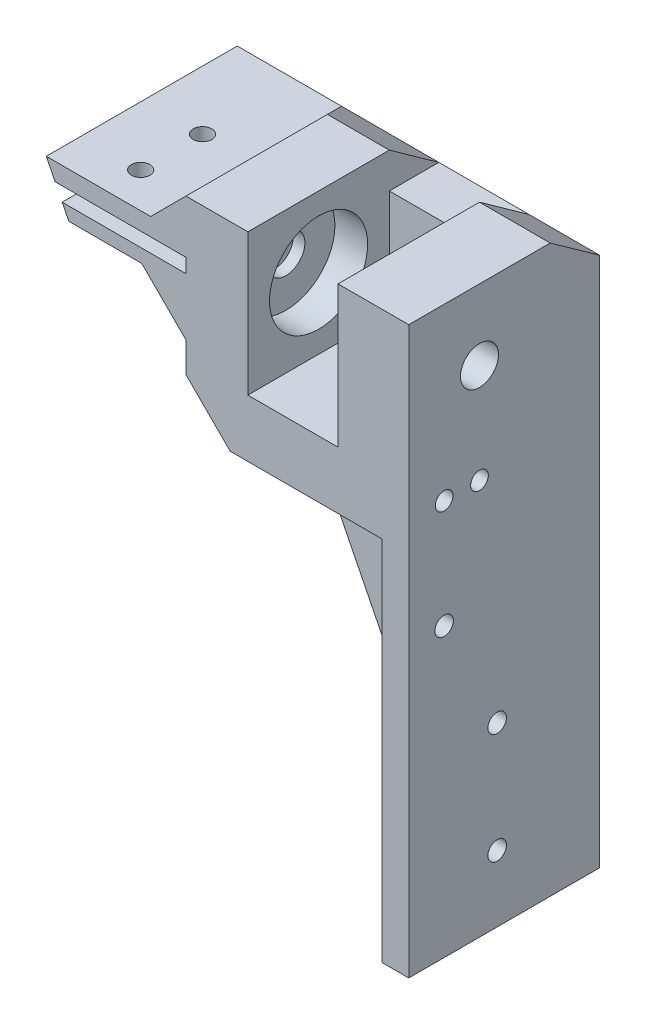
SolidWorks part; units mm, degrees
material "ABS"
ref_plane "Płaszczyzna przednia" through (0, 0, 0) normal (0, 0, 1) x (1, 0, 0)
ref_plane "Płaszczyzna górna" through (0, 0, 0) normal (0, 1, 0) x (1, 0, 0)
ref_plane "Płaszczyzna prawa" through (0, 0, 0) normal (1, 0, 0) x (0, 0, -1)
sketch "Szkic1" plane through (0, 0, 0) normal (0, 0, 1) x (1, 0, 0)
  line L0 (0, 0) -> (80, 0)
  line L1 (0, 0) -> (0, -120)
  line L2 (80, 0) -> (20, -120)
  line L3 (20, -120) -> (0, -120)
  dimension "D1" = 80
  dimension "D2" = 120
  dimension "D3" = 20
extrude "Dodanie-wyciągnięcie1" add sketch "Szkic1" along normal blind 4
sketch "Szkic2" plane through (0, 0, 4) normal (0, 0, 1) x (1, 0, 0)
  line L0 (80, 0) -> (0, 0) construction
  line L1 (0, 0) -> (0, -120) construction
  line L2 (80, 0) -> (0, 0)
  line L3 (0, 0) -> (0, -120)
  line L4 (78, -4) -> (4, -4)
  line L5 (4, -4) -> (4, -120)
  line L6 (4, -120) -> (0, -120)
  line L7 (80, 0) -> (78, -4)
  line L9 (80, -4) -> (4, -4) construction
  dimension "D1" = 4
extrude "Dodanie-wyciągnięcie2" add sketch "Szkic2" along normal blind 3.2
sketch "Szkic3" plane through (0, 0, 7.2) normal (0, 0, 1) x (1, 0, 0)
  line L0 (78, -4) -> (80, 0) construction
  line L1 (0, -120) -> (4, -120) construction
  line L2 (4, -120) -> (20, -120) construction
  line L3 (20, -120) -> (78, -4) construction
  line L4 (80, 0) -> (0, 0) construction
  line L5 (0, 0) -> (0, -120) construction
  line L6 (78, -4) -> (80, 0)
  line L7 (0, -120) -> (4, -120)
  line L8 (4, -120) -> (20, -120)
  line L9 (20, -120) -> (78, -4)
  line L10 (80, 0) -> (0, 0)
  line L11 (0, 0) -> (0, -120)
extrude "Dodanie-wyciągnięcie3" add sketch "Szkic3" along normal blind 4
sketch "Szkic4" plane through (0, 0, 11.2) normal (0, 0, 1) x (1, 0, 0)
  line L0 (0, 8) -> (0, -37)
  line L1 (0, 0) -> (0, -120) construction
  line L3 (14, -24) -> (14, 8)
  line L6 (34.4, -24) -> (34.4, 8)
  line L7 (80, 0) -> (0, 0) construction
  line L8 (48.4, 8) -> (48.4, -37)
  line L9 (0, 8) -> (14, 8)
  line L10 (34.4, 8) -> (48.4, 8)
  line L11 (0, -37) -> (48.4, -37)
  line L12 (14, -24) -> (34.4, -24)
  dimension "D1" = 45
  dimension "D2" = 14
  dimension "D3" = 20.4
  dimension "D4" = 14
  dimension "D5" = 8
  dimension "D6" = 32
extrude "Dodanie-wyciągnięcie4" add sketch "Szkic4" along normal blind 32
ref_plane "Płaszczyzna1" through (24.2, 0, 0) normal (1, 0, 0) x (0, 0, -1)
sketch "Szkic5" plane through (24.2, 0, 0) normal (1, 0, 0) x (0, 0, -1)
  line L0 (-11.2, -120) -> (-11.2, 0) construction
  line L1 (-43.2, 8) -> (-11.2, 8) construction
  circle A0 centre (-27.2, -8) radius 11.1
  dimension "D1" = 22.2
  dimension "D3" = 16
  dimension "D2" = 16
extrude "Wytnij-wyciągnięcie1" cut sketch "Szkic5" against normal blind 17.6 and the other way blind 17.6
chamfer "Sfazowanie1" distance 11.2 distance2 8 2 edges at (7, 0, 11.2) (41.4, 0, 11.2) first distance on face at (36.6857, 0, 8)
sketch "Szkic6" plane through (24.2, 0, 0) normal (1, 0, 0) x (0, 0, -1)
  circle A0 centre (-27.2, -8) radius 11.1 construction
  circle A1 centre (-27.2, -8) radius 11.1 construction
  circle A2 centre (-27.2, -8) radius 4.3
  dimension "D1" = 8.6
extrude "Wytnij-wyciągnięcie2" cut sketch "Szkic6" against normal through all and the other way blind 20.2
sketch "Szkic7" plane through (0, 0, 11.2) normal (0, 0, 1) x (1, 0, 0)
  line L0 (0, -37) -> (0, -120)
  line L1 (0, -120) -> (20, -120) construction
  line L2 (0, -37) -> (0, -120) construction
  line L3 (0, -120) -> (4, -120)
  line L4 (4, -120) -> (4, -37)
  line L5 (0, -37) -> (48.4, -37) construction
  line L6 (4, -37) -> (0, -37)
  line L11 (0, -37) -> (48.4, -37) construction
  line L12 (7.2, -37) -> (10.2, -37)
  line L13 (7.2, -37) -> (7.2, -120)
  line L14 (7.2, -120) -> (10.2, -120)
  line L15 (10.2, -37) -> (10.2, -120)
  line L16 (48.4, 0) -> (80, 0)
  line L17 (80, 0) -> (78, -4)
  line L18 (20, -120) -> (80, 0) construction
  line L19 (78, -4) -> (48.4, -4)
  line L20 (48.4, -37) -> (48.4, 0) construction
  line L21 (48.4, -4) -> (48.4, 0)
  line L22 (48.4, -7.2) -> (76.4, -7.2)
  line L23 (76.4, -7.2) -> (74.9, -10.2)
  line L24 (74.9, -10.2) -> (48.4, -10.2)
  line L25 (48.4, -10.2) -> (48.4, -7.2)
  dimension "D1" = 4
  dimension "D2" = 3
  dimension "D3" = 3.2
  dimension "D4" = 4
  dimension "D5" = 3
  dimension "D6" = 3.2
extrude "Dodanie-wyciągnięcie5" add sketch "Szkic7" along normal blind 32
chamfer "Sfazowanie2" distance 10 angle 45 3 edges at (48.4, -37, 27.2) (48.4, -10.2, 27.2) (10.2, -37, 27.2)
chamfer "Sfazowanie3" distance 2 angle 70 7 edges at (66.65, -10.2, 11.2) (53.4, -15.2, 11.2) (48.4, -23.6, 11.2) (43.4, -32, 11.2) (29.3, -37, 11.2) (15.2, -42, 11.2) (10.2, -83.5, 11.2) first distance on face at (36.5667, -47.6222, 11.2)
sketch "Szkic8" plane through (0, -10.2, 0) normal (0, -1, 0) x (1, 0, 0)
  line L0 (58.4, 43.2) -> (74.9, 43.2) construction
  line L1 (20, 11.2) -> (73.9, 11.2) construction
  line L2 (58.4, 43.2) -> (58.4, 16.695) construction
  circle A0 centre (66.65, 35.2) radius 2.1
  circle A1 centre (66.65, 21.2) radius 2.1
  dimension "D3" = 4.2
  dimension "D1" = 8
  dimension "D2" = 10
  dimension "D4" = 8.25
extrude "Otwory tyl" cut sketch "Szkic8" against normal through all
sketch "Szkic9" plane through (0, 0, 11.2) normal (0, 0, 1) x (1, 0, 0)
  line L0 (50.4, -21.0284) -> (50.4, -27.8284) construction
  line L1 (73.9, -12.2) -> (59.2284, -12.2) construction
  line L2 (12.2, -47.8284) -> (12.2, -120) construction
  line L3 (39.2284, -39) -> (21.0284, -39) construction
  circle A0 centre (60.4, -22.2) radius 3.1
  circle A1 centre (22.2, -49) radius 2.1
  circle A2 centre (22.2, -89) radius 2.1
  circle A3 centre (36.2, -49) radius 2.1
  dimension "D1" = 4.2
  dimension "D2" = 6.2
  dimension "D3" = 10
  dimension "D4" = 10
  dimension "D5" = 10
  dimension "D6" = 40
  dimension "D7" = 14
  dimension "D8" = 10
extrude "Otwory spod" cut sketch "Szkic9" against normal through all
sketch "Szkic10" plane through (10.2, 0, 0) normal (1, 0, 0) x (0, 0, -1)
  line L0 (-43.2, -120) -> (-43.2, -47) construction
  line L1 (-11.2, -47.8284) -> (-11.2, -120) construction
  line L2 (-16.695, -47) -> (-43.2, -47) construction
  circle A0 centre (-23.2, -80) radius 2.1
  circle A1 centre (-35.2, -55) radius 2.1
  circle A2 centre (-23.2, -105) radius 2.1
  dimension "D7" = 4.2
  dimension "D1" = 8
  dimension "D2" = 12
  dimension "D3" = 8
  dimension "D4" = 25
  dimension "D5" = 25
  dimension "D6" = 12
extrude "Otwory bok" cut sketch "Szkic10" against normal through all
chamfer "Sfazowanie4" distance 8 angle 45 1 edges at (48.4, 0, 21.6)
sketch "Szkic12" plane through (0, 0, 43.2) normal (0, 0, 1) x (1, 0, 0)
  line L1 (7.2, -37) -> (21.0284, -37)
  line L2 (7.2, -37) -> (7.2, -124.1298)
  line L3 (7.2, -124.1298) -> (21.0284, -124.1298)
  line L4 (21.0284, -37) -> (21.0284, -124.1298)
extrude "Wytnij-wyciągnięcie5" cut sketch "Szkic12" against normal up to surface (32 mm away) up to face at (63.5, -22.2, 11.2)
sketch "Szkic13" plane through (0, 0, 0) normal (-1, 0, 0) x (0, 0, 1)
  line L5 (0, -120) -> (43.2, -120)
  line L6 (43.2, -120) -> (43.2, 8)
  line L7 (43.2, 8) -> (11.2, 8)
  line L8 (11.2, 8) -> (0, 0)
  line L9 (0, 0) -> (0, -120)
  line L10 (0, -120) -> (43.2, -120)
  line L11 (43.2, -120) -> (43.2, 8)
  line L12 (43.2, 8) -> (11.2, 8)
  line L13 (11.2, 8) -> (0, 0)
  line L14 (0, 0) -> (0, -120)
  circle A0 centre (23.2, -105) radius 2.1 construction
  circle A1 centre (23.2, -80) radius 2.1 construction
  circle A2 centre (35.2, -55) radius 2.1 construction
  circle A3 centre (27.2, -8) radius 4.3 construction
  circle A4 centre (23.2, -105) radius 2.1
  circle A5 centre (23.2, -80) radius 2.1
  circle A6 centre (35.2, -55) radius 2.1
  circle A7 centre (27.2, -8) radius 4.3
  dimension "D1" = 0
extrude "Dodanie-wyciągnięcie6" add sketch "Szkic13" along normal blind 2
sketch "Szkic14" plane through (-2, 0, 0) normal (-1, 0, 0) x (0, 0, 1)
  line L0 (43.2, -37) -> (11.2, -37) construction
  line L1 (43.2, -37) -> (11.2, -37)
  line L2 (43.2, -24) -> (11.2, -24) construction
  line L3 (43.2, -24) -> (11.2, -24)
  line L4 (43.2, -120) -> (43.2, 8) construction
  circle A0 centre (35.2, -30.5) radius 2
  circle A1 centre (27.2, -30.5) radius 2
  dimension "D1" = 4
  dimension "D3" = 8
  dimension "D4" = 4
  dimension "D2" = 8
  dimension "D5" = 6.5
extrude "Wytnij-wyciągnięcie6" cut sketch "Szkic14" against normal blind 5 contours A1 | A0 region at (-2, -30.5, 35.2) region at (-2, -30.5, 27.2)
mirror "Lustro2" about plane through (-2, 0, 0) normal (-1, 0, 0) of bodies 115
sketch "Szkic15" plane through (0, -120, 0) normal (0, -1, 0) x (1, 0, 0)
  line L1 (-2, 0) -> (92.3505, 0)
  line L2 (-2, 0) -> (-2, 51.4777)
  line L3 (-2, 51.4777) -> (92.3505, 51.4777)
  line L4 (92.3505, 0) -> (92.3505, 51.4777)
extrude "Wytnij-wyciągnięcie7" cut sketch "Szkic15" against normal through all
